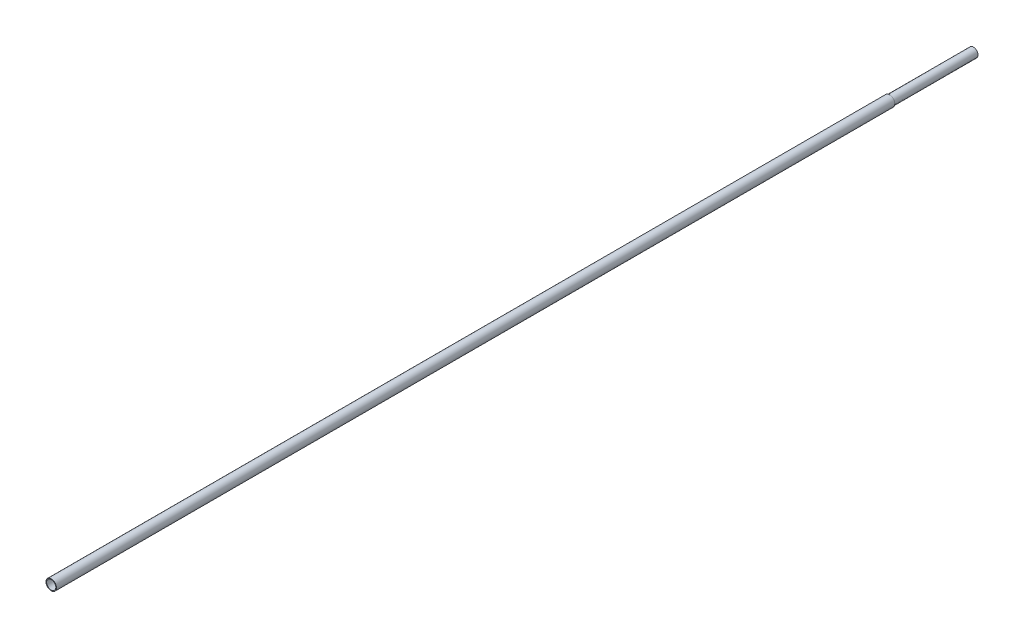
SolidWorks part; units mm, degrees
ref_plane "Front" through (0, 0, 0) normal (0, 0, 1) x (1, 0, 0)
ref_plane "Top" through (0, 0, 0) normal (0, 1, 0) x (1, 0, 0)
ref_plane "Right" through (0, 0, 0) normal (1, 0, 0) x (0, 0, -1)
sketch "Sketch1" plane through (0, 0, 0) normal (0, 0, 1) x (1, 0, 0)
  circle A0 centre (0, 0) radius 22.225
  circle A1 centre (0, 0) radius 25.4
  dimension "D1" = 50.8
  dimension "D2" = 44.45
extrude "Boss-Extrude1" add sketch "Sketch1" along normal blind 4064
sketch "Sketch2" plane through (0, 0, 0) normal (0, 1, 0) x (1, 0, 0)
  line L0 (0, 0) -> (0, -152.4) construction
  circle A0 centre (0, -152.4) radius 6.35
  dimension "D1" = 12.7
  dimension "D2" = 152.4
extrude "Cut-Extrude1" cut sketch "Sketch2" against normal through all
ref_axis "Axis1" through (0, 0, 4064) along (0, 0, -1)
pattern_linear "LPattern1" count 8 spacing 25.4 along (0, 0, 1) of "Cut-Extrude1"
pattern_linear "LPattern2" count 8 spacing 609.6 along (0, 0, 1) of "LPattern1"
sketch "Sketch3" plane through (0, 0, 0) normal (0, 0, -1) x (-1, 0, 0)
  circle A0 centre (0, 0) radius 19.05
  circle A1 centre (0, 0) radius 22.225 construction
  circle A2 centre (0, 0) radius 22.225
  dimension "D1" = 38.1
extrude "Boss-Extrude2" add sketch "Sketch3" along normal blind 406.4 separate body
